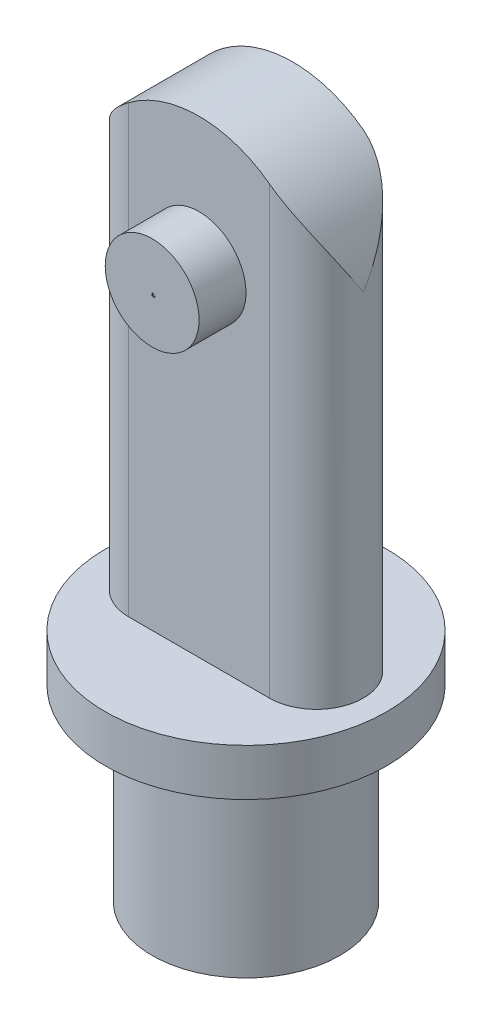
SolidWorks part; units mm, degrees
ref_plane "Front Plane" through (0, 0, 0) normal (0, 0, 1) x (1, 0, 0)
ref_plane "Top Plane" through (0, 0, 0) normal (0, 1, 0) x (1, 0, 0)
ref_plane "Right Plane" through (0, 0, 0) normal (1, 0, 0) x (0, 0, -1)
sketch "Sketch4" plane through (0, 0, 0) normal (0, 0, 1) x (1, 0, 0)
  line L0 (0, -148.1481) -> (100, -148.1481)
  line L1 (100, -148.1481) -> (100, 51.8519)
  line L2 (100, 51.8519) -> (150, 51.8519)
  line L3 (150, 51.8519) -> (150, 101.8519)
  line L4 (150, 101.8519) -> (0, 101.8519)
  line L5 (0, 101.8519) -> (0, -148.1481)
  dimension "D1" = 100
  dimension "D2" = 50
  dimension "D3" = 50
  dimension "D4" = 250
revolve "Revolve1" add sketch "Sketch4" angle 360 about L5 region at (56.8182, -14.0572, 0)
sketch "Sketch7" plane through (0, 101.8519, 0) normal (0, 1, 0) x (1, 0, 0)
  line L1 (-75, 50) -> (75, 50)
  line L3 (-75, -50) -> (75, -50)
  arc A0 (-75, 50) -> (-75, -50) centre (-75, 0) ccw
  arc A1 (75, -50) -> (75, 50) centre (75, 0) ccw
  point P0 (0, 0)
  dimension "D3" = 100
  dimension "D4" = 100
  dimension "D1" = 150
  dimension "D2" = 100
extrude "Boss-Extrude1" add sketch "Sketch7" along normal blind 500
sketch "Sketch8" plane through (0, 0, 50) normal (0, 0, 1) x (1, 0, 0)
  line L0 (125, 601.8519) -> (75, 601.8519) construction
  line L1 (-125, 476.3519) -> (-125, 601.8519)
  line L2 (-125, 601.8519) -> (125, 2101.8519)
  line L3 (125, 2101.8519) -> (125, 476.3519)
  arc A0 (125, 476.3519) -> (-125, 476.3519) centre (0, 476.3519) ccw
  dimension "D1" = 250
  dimension "D2" = 125.5
extrude "Cut-Extrude1" cut sketch "Sketch8" against normal blind 100
ref_axis "Link_1_Axis" through (0, 638.8269, 0) along (0, -1, 0)
sketch "Sketch9" plane through (0, 0, 50) normal (0, 0, 1) x (1, 0, 0)
  line L0 (0, 638.8269) -> (0, -185.6231) construction
  circle A0 centre (0, 463.3) radius 50
  dimension "D1" = 463.3
extrude "Boss-Extrude2" add sketch "Sketch9" along normal blind 50
sketch "Sketch10" plane through (0, 0, 100) normal (0, 0, 1) x (1, 0, 0)
  line L1 (0, 463.3) -> (3.0904, 463.3)
  line L2 (0, 463.3) -> (0, 460.3069)
  line L3 (0, 460.3069) -> (3.0904, 460.3069)
  line L4 (3.0904, 463.3) -> (3.0904, 460.3069)
extrude "Cut-Extrude2" cut sketch "Sketch10" against normal blind 1
